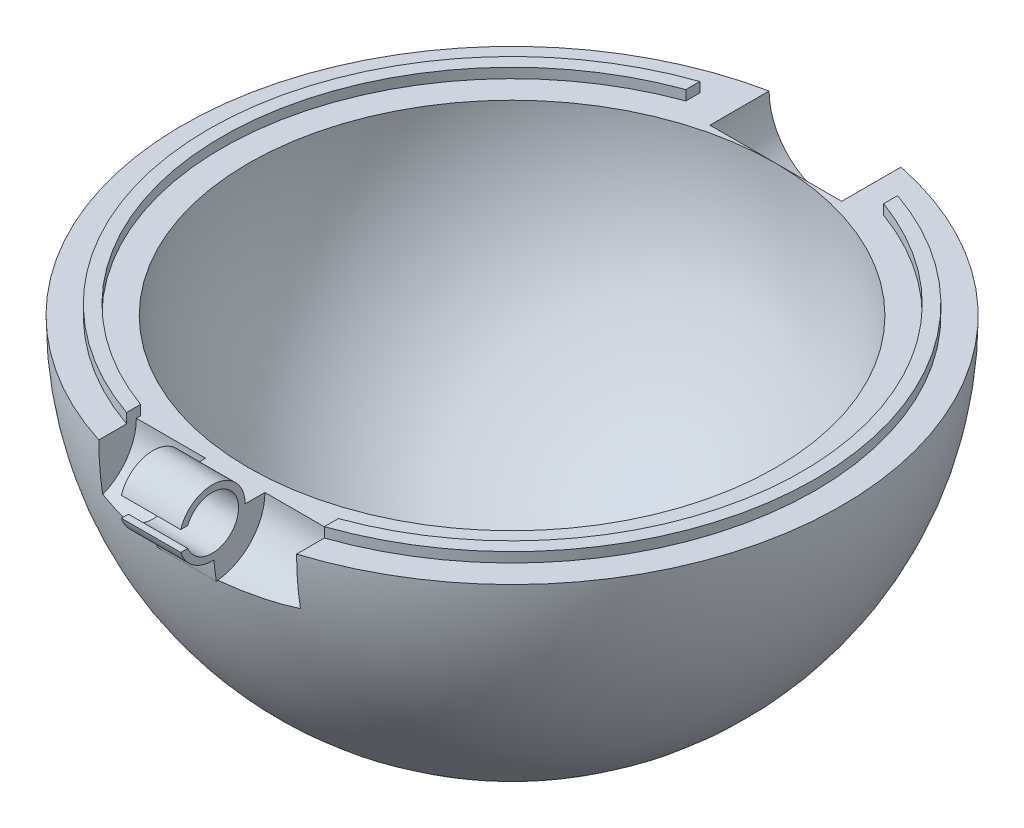
SolidWorks part; units mm, degrees
ref_plane "Front Plane" through (0, 0, 0) normal (0, 0, 1) x (1, 0, 0)
ref_plane "Top Plane" through (0, 0, 0) normal (0, 1, 0) x (1, 0, 0)
ref_plane "Right Plane" through (0, 0, 0) normal (1, 0, 0) x (0, 0, -1)
sketch "Sketch1" plane through (0, 0, 0) normal (1, 0, 0) x (0, 0, -1)
  line L0 (0, -40) -> (0, -50)
  line L1 (40, 0) -> (50, 0)
  line L2 (0, 58.0686) -> (0, -58.0686) construction
  arc A0 (0, -50) -> (50, 0) centre (0, 0) ccw
  arc A1 (0, -40) -> (40, 0) centre (0, 0) ccw
  point P8 (0, 0)
  point P9 (0, 0)
revolve "Revolve1" add sketch "Sketch1" angle 360 about L2
sketch "Sketch2" plane through (0, 0, 0) normal (1, 0, 0) x (0, 0, -1)
  circle A0 centre (-50, 0) radius 8
extrude "Cut-Extrude1" cut sketch "Sketch2" against normal blind 15 and the other way blind 15
sketch "Sketch3" plane through (0, 0, 0) normal (1, 0, 0) x (0, 0, -1)
  circle A0 centre (-50, 0) radius 5
  circle A1 centre (-50, 0) radius 4
extrude "Boss-Extrude1" add sketch "Sketch3" along normal blind 4.5 and the other way blind 4.5 separate body
sketch "Sketch4" plane through (0, 0, 0) normal (1, 0, 0) x (0, 0, -1)
  line L1 (-46, 0) -> (-40, 0)
  line L2 (-50, -4) -> (-50, -5)
  line L3 (-50, -5) -> (-40, -5)
  line L4 (-40, 0) -> (-40, -5)
  arc A0 (-50, -4) -> (-46, 0) centre (-50, 0) ccw
extrude "Boss-Extrude2" add sketch "Sketch4" along normal blind 4.5 and the other way blind 4.5
ref_plane "Plane1" through (0, 0, -50) normal (0, 0, 1) x (1, 0, 0)
sketch "Sketch5" plane through (0, 0, -50) normal (0, 0, 1) x (1, 0, 0)
  circle A0 centre (0, 0) radius 10
extrude "Cut-Extrude2" cut sketch "Sketch5" along normal blind 10
sketch "Sketch6" plane through (0, 0, 0) normal (0, 1, 0) x (1, 0, 0)
  line L0 (-15, 52.4033) -> (-15, -57.5584) construction
  line L1 (15, 55.195) -> (15, -56.3177) construction
  line L2 (0, 0) -> (0, 63.6073) construction
  line L3 (-15, 43.4856) -> (-15, 41.3642)
  line L4 (15, 43.4856) -> (15, 41.3642)
  line L5 (-15, -41.3642) -> (-15, -43.4856)
  line L6 (15, -41.3642) -> (15, -43.4856)
  arc A0 (-15, 43.4856) -> (-15, -43.4856) centre (0, 0) ccw
  arc A1 (-15, 41.3642) -> (-15, -41.3642) centre (0, 0) ccw
  arc A2 (15, -41.3642) -> (15, 41.3642) centre (0, 0) ccw
  arc A3 (15, -43.4856) -> (15, 43.4856) centre (0, 0) ccw
  dimension "D1" = 30
  dimension "D2" = 15
extrude "Boss-Extrude3" add sketch "Sketch6" along normal blind 1.5
sketch "Sketch10" plane through (0, 0, 0) normal (1, 0, 0) x (0, 0, -1)
  line L1 (-49.7494, -5) -> (-40, -5)
  line L3 (-49.3559, -8) -> (-40, -8)
  line L4 (-40, -5) -> (-40, -8)
  arc A0 (-49.7494, -5) -> (-49.3559, -8) centre (0, 0) ccw
extrude "Boss-Extrude6" add sketch "Sketch10" along normal blind 4.5 and the other way blind 4.5
sketch "Sketch11" plane through (0, 0, 0) normal (1, 0, 0) x (0, 0, -1)
  line L1 (-60, 1.5) -> (-50, 1.5)
  line L2 (-60, 1.5) -> (-60, -1.5)
  line L3 (-60, -1.5) -> (-50, -1.5)
  line L4 (-50, 1.5) -> (-50, -1.5)
extrude "Cut-Extrude3" cut sketch "Sketch11" against normal blind 4.5 and the other way blind 4.5
ref_plane "Plane2" through (0, -50, 0) normal (0, 1, 0) x (1, 0, 0)
sketch "Sketch12" plane through (0, -50, 0) normal (0, 1, 0) x (1, 0, 0)
  circle A0 centre (0, 0) radius 10
extrude "Cut-Extrude4" cut sketch "Sketch12" along normal blind 1
